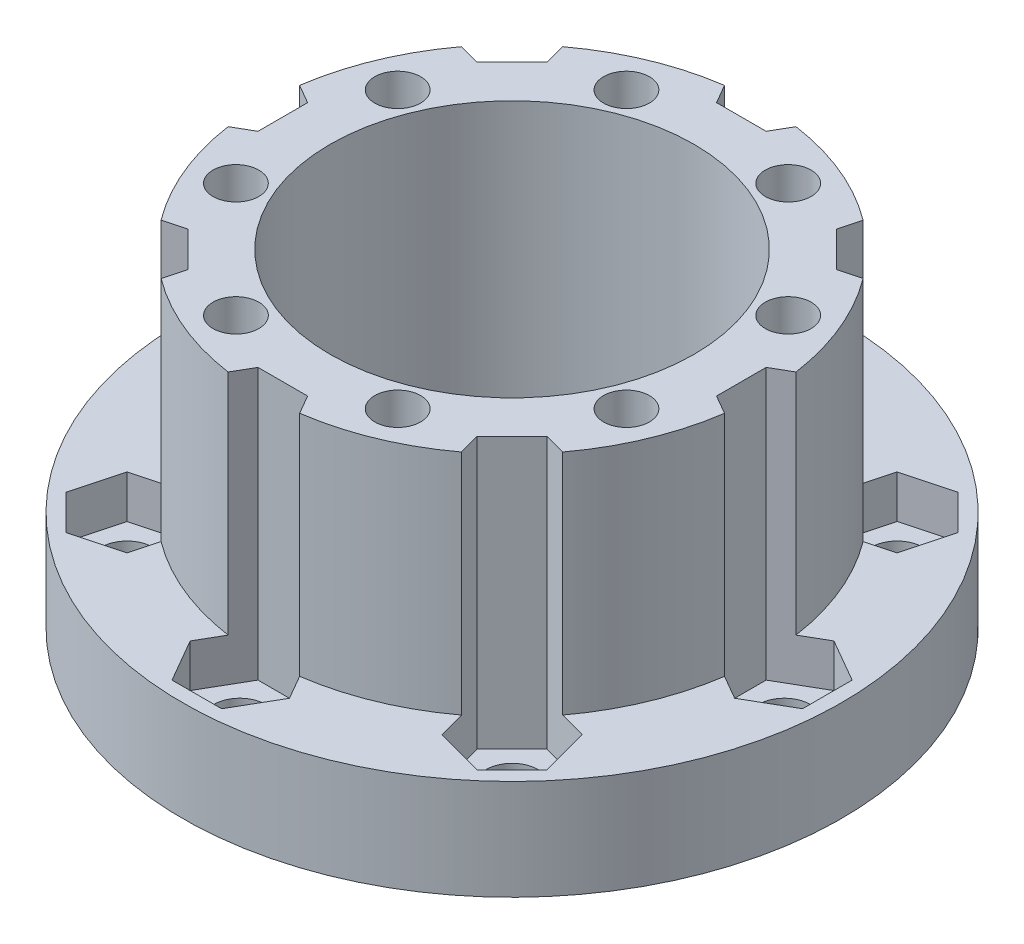
SolidWorks part; units mm, degrees
material "6061-T6 (SS)"
ref_plane "前视基准面" through (0, 0, 0) normal (0, 0, 1) x (1, 0, 0)
ref_plane "上视基准面" through (0, 0, 0) normal (0, 1, 0) x (1, 0, 0)
ref_plane "右视基准面" through (0, 0, 0) normal (1, 0, 0) x (0, 0, -1)
sketch "草图1" plane through (0, 0, 0) normal (0, 0, 1) x (1, 0, 0)
  line L0 (0, 0) -> (0, 36.8725) construction
  line L1 (-12, 0) -> (-16.9, 0)
  line L2 (-16.9, 0) -> (-16.9, 2)
  line L3 (-16.9, 2) -> (-23, 2)
  line L4 (-23, 2) -> (-23, 9)
  line L5 (-23, 9) -> (-17.5, 9)
  line L6 (-17.5, 9) -> (-17.5, 27)
  line L7 (-17.5, 27) -> (-6.75, 27)
  line L8 (-6.75, 27) -> (-6.75, 25)
  line L9 (-6.75, 25) -> (-12, 25)
  line L10 (-12, 25) -> (-12, 0)
  dimension "D1" = 24
  dimension "D2" = 4.9
  dimension "D3" = 35
  dimension "D4" = 2
  dimension "D5" = 46
  dimension "D6" = 7
  dimension "D7" = 90
  dimension "D8" = 2
  dimension "D9" = 25
  dimension "D10" = 13.5
revolve "旋转1" add sketch "草图1" angle 360 about L0
sketch "草图2" plane through (0, 2, 0) normal (0, -1, 0) x (1, 0, 0)
  circle A0 centre (0, 0) radius 19 construction
  circle A1 centre (0, -19) radius 1.8
  dimension "D1" = 38
  dimension "D2" = 3.6
extrude "切除-拉伸1" cut sketch "草图2" against normal blind 8
sketch "草图4" plane through (0, 9, 0) normal (0, 1, 0) x (1, 0, 0)
  line L1 (-1.7321, 22) -> (-3.4641, 19)
  line L2 (-3.4641, 19) -> (-1.7321, 16)
  line L3 (-1.7321, 16) -> (1.7321, 16)
  line L4 (1.7321, 16) -> (3.4641, 19)
  line L5 (3.4641, 19) -> (1.7321, 22)
  line L6 (1.7321, 22) -> (-1.7321, 22)
  circle A0 centre (0, 19) radius 3 construction
  dimension "D1" = 6
extrude "切除-拉伸3" cut sketch "草图4" against normal blind 3 and the other way through all
pattern_circular "阵列(圆周)1" count 8 over 360 about axis through (0, 2, 0) along (0, -1, 0) of "切除-拉伸1", "切除-拉伸3"
sketch "草图3" plane through (0, 27, 0) normal (0, 1, 0) x (1, 0, 0)
  circle A0 centre (0, 0) radius 9.5 construction
  circle A1 centre (0, -9.5) radius 1.55
  circle A2 centre (-8.2272, 4.75) radius 1.55
  circle A3 centre (8.2272, 4.75) radius 1.55
  point P11 (0, 0)
  dimension "D1" = 19
  dimension "D2" = 3.1
  dimension "D3" = 3
extrude "切除-拉伸2" cut sketch "草图3" against normal blind 10
sketch "草图5" plane through (0, 0, 0) normal (0, 0, 1) x (1, 0, 0)
  line L1 (-17.5, 25) -> (17.5, 25)
  line L2 (-17.5, 25) -> (-17.5, 24.9)
  line L3 (-17.5, 24.9) -> (17.5, 24.9)
  line L4 (17.5, 25) -> (17.5, 24.9)
  line L6 (17.5, 27) -> (-17.5, 27) construction
  dimension "D1" = 2
  dimension "D2" = 0.1
  dimension "D3" = 17.5
  dimension "D4" = 17.5
extrude "切除-拉伸4" cut sketch "草图5" against normal through all both and the other way through all
sketch "草图6" plane through (0, 27, 0) normal (0, 1, 0) x (1, 0, 0)
  line L0 (5.6446, 13.6272) -> (0, 0) construction
  line L1 (0, 0) -> (0, 19) construction
  circle A0 centre (0, 0) radius 14.75 construction
  circle A1 centre (5.6446, 13.6272) radius 1.6
  dimension "D1" = 29.5
  dimension "D2" = 3.2
  dimension "D3" = 22.5
extrude "切除-拉伸5" cut sketch "草图6" against normal through all
pattern_circular "阵列(圆周)2" count 8 over 360 about axis through (0, 0, 0) along (0, -1, 0) of "切除-拉伸5" reverse direction yes
delete or keep bodies "实体-删除/保留 1" type delete bodies bodies 116
sketch "草图7" plane through (0, 24.9, 0) normal (0, 1, 0) x (1, 0, 0)
  circle A0 centre (0, 0) radius 12.7
  dimension "D1" = 25.4
extrude "切除-拉伸6" cut sketch "草图7" against normal through all
